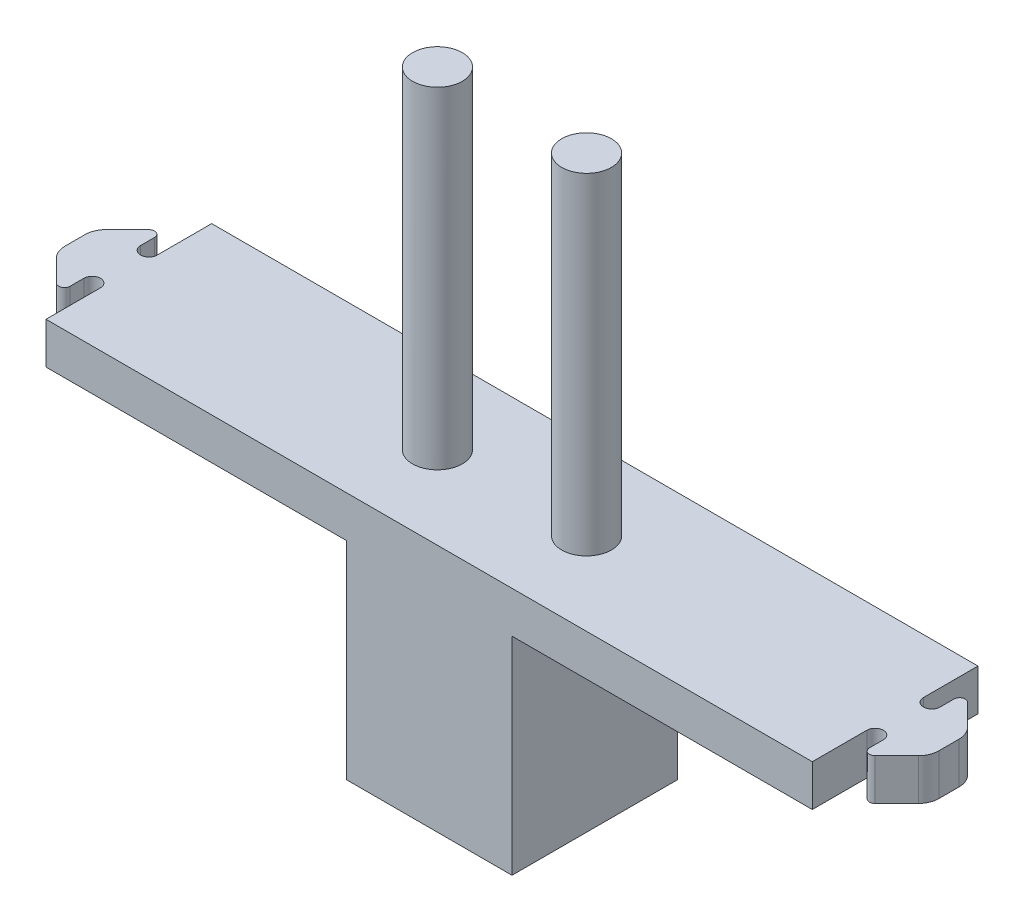
SolidWorks part; units mm, degrees
ref_plane "Front Plane" through (0, 0, 0) normal (0, 0, 1) x (1, 0, 0)
ref_plane "Top Plane" through (0, 0, 0) normal (0, 1, 0) x (1, 0, 0)
ref_plane "Right Plane" through (0, 0, 0) normal (1, 0, 0) x (0, 0, -1)
sketch "Sketch1" plane through (0, 0, 0) normal (0, 1, 0) x (1, 0, 0)
  line L0 (12.1572, -15.7678) -> (7.8138, -15.7678)
  line L1 (0, 0) -> (-117.475, 0)
  line L2 (0, 0) -> (0, -25.4)
  line L3 (0, -25.4) -> (-117.475, -25.4)
  line L4 (-117.475, 0) -> (-117.475, -25.4)
  line L13 (7.8138, -13.2278) -> (5.6802, -13.2278)
  line L14 (5.0695, -11.7535) -> (8.3922, -8.4308)
  line L15 (10.6437, -7.5166) -> (12.1572, -7.5166)
  line L16 (12.1572, -7.5166) -> (12.1572, -15.7678)
  arc A0 (7.8138, -15.7678) -> (7.8138, -13.2278) centre (7.8138, -14.4978) ccw
  arc A1 (5.6802, -13.2278) -> (5.0695, -11.7535) centre (5.6802, -12.3642) cw
  arc A2 (8.3922, -8.4308) -> (10.6437, -7.5166) centre (10.6216, -10.6915) cw
  point P18 (11.4004, -7.5166)
  dimension "D5" = 6.477
  dimension "D7" = 1.27
  dimension "D8" = 0.8636
  dimension "D9" = 3.175
  dimension "D1" = 117.475
  dimension "D2" = 25.4
  dimension "D3" = 4.3434
  dimension "D4" = 8.2512
  dimension "D6" = 45
  dimension "D10" = 2.54
  dimension "D11" = 3.4036
  dimension "D12" = 5.0763
  dimension "D13" = 1.5356
  dimension "D14" = 4.3434
  dimension "D15" = 4.0143
extrude "Boss-Extrude1" add sketch "Sketch1" along normal blind 6.35 contours L1 L4 L3 L2
sketch "Sketch3" plane through (0, 6.35, 0) normal (0, 1, 0) x (1, 0, 0)
  line L0 (0, 0) -> (-117.475, 0) construction
  line L1 (-114.3, 0) -> (-3.175, 0)
  line L2 (-114.3, 0) -> (-114.3, -25.4)
  line L3 (-114.3, -25.4) -> (-3.175, -25.4)
  line L4 (-3.175, 0) -> (-3.175, -25.4)
  line L5 (0, -25.4) -> (-117.475, -25.4) construction
  line L6 (0, -25.4) -> (-117.475, -25.4) construction
  circle A0 centre (-47.3075, -12.7) radius 3.81
  circle A1 centre (-70.1675, -12.7) radius 3.81
  point P8 (-58.7375, 0)
  point P11 (-58.7375, -25.4)
  dimension "D3" = 12.7
  dimension "D7" = 7.62
  dimension "D8" = 7.62
  dimension "D1" = 111.125
  dimension "D2" = 0
  dimension "D4" = 11.43
  dimension "D5" = 12.7
  dimension "D6" = 11.43
extrude "Boss-Extrude2" add sketch "Sketch3" along normal blind 50.8 contours A0 | A1
ref_plane "Plane1" through (-58.7375, 0, 0) normal (-1, 0, 0) x (0, 0, 1)
sketch "Sketch10" plane through (0, 6.35, 0) normal (0, 1, 0) x (1, 0, 0)
  line L5 (0, -12.7) -> (0, -8.3566)
  line L6 (2.54, -8.3566) -> (2.54, -6.223)
  line L7 (4.0143, -5.6123) -> (7.337, -8.935)
  line L8 (8.2512, -11.1865) -> (8.2512, -12.7)
  line L9 (8.2512, -12.7) -> (0, -12.7)
  line L10 (-58.7375, 3.4925) -> (-58.7375, -3.4925) construction
  line L11 (0, 0) -> (0, -25.4) construction
  line L12 (-117.475, -12.7) -> (-117.475, -8.3566)
  line L13 (-120.015, -8.3566) -> (-120.015, -6.223)
  line L14 (-121.4893, -5.6123) -> (-124.812, -8.935)
  line L15 (-125.7262, -11.1865) -> (-125.7262, -12.7)
  line L16 (-125.7262, -12.7) -> (-117.475, -12.7)
  arc A3 (0, -8.3566) -> (2.54, -8.3566) centre (1.27, -8.3566) ccw
  arc A4 (2.54, -6.223) -> (4.0143, -5.6123) centre (3.4036, -6.223) cw
  arc A5 (7.337, -8.935) -> (8.2512, -11.1865) centre (5.0763, -11.1644) cw
  arc A6 (-117.475, -8.3566) -> (-120.015, -8.3566) centre (-118.745, -8.3566) cw
  arc A7 (-120.015, -6.223) -> (-121.4893, -5.6123) centre (-120.8786, -6.223) ccw
  arc A8 (-124.812, -8.935) -> (-125.7262, -11.1865) centre (-122.5513, -11.1644) ccw
  point P2 (0, -12.7)
extrude "Boss-Extrude7" add sketch "Sketch10" against normal blind 6.35
mirror "Mirror1" about plane through (8.2512, 0, 12.7) normal (0, 0, 1) of "Boss-Extrude7"
sketch "Sketch12" plane through (0, 0, 0) normal (0, -1, 0) x (-1, 0, 0)
  line L0 (0, -25.4) -> (117.475, -25.4) construction
  line L1 (71.4375, -25.4) -> (46.0375, -25.4)
  line L2 (71.4375, -25.4) -> (71.4375, 0)
  line L3 (71.4375, 0) -> (46.0375, 0)
  line L4 (46.0375, -25.4) -> (46.0375, 0)
  line L5 (0, 0) -> (117.475, 0) construction
  point P8 (58.7375, 0)
  point P9 (58.7375, 0)
  dimension "D1" = 25.4
extrude "Boss-Extrude8" add sketch "Sketch12" along normal blind 31.75 contours L2 L1 L4 L3
